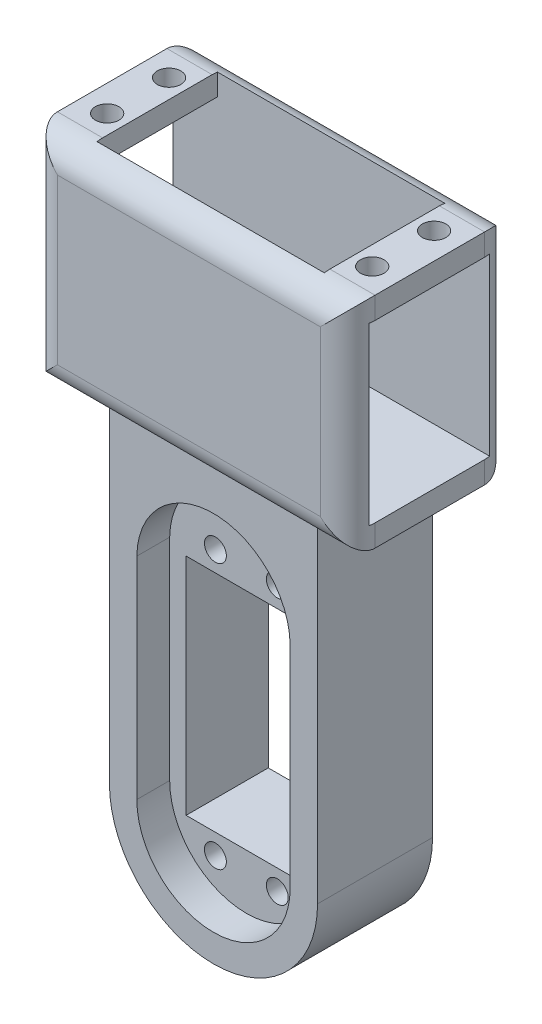
SolidWorks part; units mm, degrees
ref_plane "Front Plane" through (0, 0, 0) normal (0, 0, 1) x (1, 0, 0)
ref_plane "Top Plane" through (0, 0, 0) normal (0, 1, 0) x (1, 0, 0)
ref_plane "Right Plane" through (0, 0, 0) normal (1, 0, 0) x (0, 0, -1)
sketch "Sketch1" plane through (0, 0, 0) normal (0, 0, 1) x (1, 0, 0)
  line L1 (0, 0) -> (38, 0)
  line L2 (0, 0) -> (0, 120)
  line L3 (0, 120) -> (38, 120)
  line L4 (38, 0) -> (38, 120)
  dimension "D1" = 120
  dimension "D2" = 38
extrude "Boss-Extrude1" add sketch "Sketch1" along normal blind 13
fillet "Fillet1" radius 19 2 edges at (38, 0, 6.5) (0, 0, 6.5)
sketch "Sketch2" plane through (0, 0, 13) normal (0, 0, 1) x (1, 0, 0)
  line L0 (33, 19) -> (33, 115)
  line L1 (33, 115) -> (5, 115)
  line L2 (5, 115) -> (5, 19)
  line L3 (38, 19) -> (38, 120)
  line L4 (38, 120) -> (0, 120)
  line L5 (0, 120) -> (0, 19)
  line L6 (38, 19) -> (38, 120)
  line L7 (38, 120) -> (0, 120)
  line L8 (0, 120) -> (0, 19)
  line L9 (38, 72) -> (0, 72)
  arc A0 (5, 19) -> (19, 5) centre (19, 19) ccw
  arc A1 (19, 5) -> (33, 19) centre (19, 19) ccw
  arc A2 (0, 19) -> (19, 0) centre (19, 19) ccw
  arc A3 (19, 0) -> (38, 19) centre (19, 19) ccw
  arc A4 (0, 19) -> (19, 0) centre (19, 19) ccw
  arc A6 (19, 0) -> (38, 19) centre (19, 19) ccw construction
  arc A7 (19, 0) -> (38, 19) centre (19, 19) ccw
  arc A8 (19, 0) -> (38, 19) centre (19, 19) ccw construction
  point P15 (33, 67)
  arc M11 (0, 19) -> (19, 0) centre (19, 19) ccw
  arc M12 (19, 0) -> (38, 19) centre (19, 19) ccw
  line M13 (38, 19) -> (38, 120)
  line M14 (38, 120) -> (0, 120)
  line M15 (0, 120) -> (0, 19)
  dimension "D3" = 5
  dimension "D1" = 0
  dimension "D2" = 5
extrude "Boss-Extrude2" add sketch "Sketch2" along normal blind 8 contours A1 A0 L2 L9 L8 L0 M11 M12 M13 | L9 L6 L2 L1 L0 M14 M15 | L9 L0 L1 L2 region at (33.8141, 45.5, 13) region at (19, 93.5, 13) region at (33.6122, 93.5, 13)
sketch "Sketch3" plane through (0, 0, 13) normal (0, 0, 1) x (1, 0, 0)
  line L1 (5, 57) -> (5, 19)
  line L2 (33, 19) -> (33, 57)
  line L3 (5, 72) -> (5, 19) construction
  line L6 (33, 72) -> (5, 72)
  line L7 (5, 72) -> (5, 19)
  line L8 (33, 19) -> (33, 72)
  line L9 (33, 72) -> (5, 72)
  line L10 (5, 72) -> (5, 19)
  line L11 (33, 19) -> (33, 72)
  arc A7 (33, 57) -> (5, 57) centre (19, 57.2426) ccw
  arc A9 (5, 19) -> (33, 19) centre (19, 19) ccw
  arc A11 (5, 19) -> (33, 19) centre (19, 19) ccw
  arc A12 (5, 19) -> (33, 19) centre (19, 19) ccw
  arc A13 (5, 19) -> (33, 19) centre (19, 19) ccw construction
  arc M8 (5, 19) -> (33, 19) centre (19, 19) ccw
  line M9 (33, 19) -> (33, 72)
  line M11 (5, 72) -> (5, 19)
  line M21 (33, 72) -> (5, 72)
  dimension "D2" = 14.0021
  dimension "38" = 38
  dimension "D8" = 0
sketch "Sketch4" plane through (0, 120, 0) normal (0, 1, 0) x (1, 0, 0)
  line L0 (19, -21) -> (19, 30) construction
  line L1 (-10, 4.5) -> (48, 4.5)
  line L2 (-10, 4.5) -> (-10, -25.5)
  line L3 (-10, -25.5) -> (48, -25.5)
  line L4 (48, 4.5) -> (48, -25.5)
  line L5 (38, -21) -> (0, -21) construction
  line L6 (38, -10.5) -> (53.9489, -10.5) construction
  line L7 (38, -21) -> (38, 0) construction
  line L8 (48, -10.5) -> (49.4174, -10.5) construction
  line L15 (19, -21.5) -> (19, 0.5) construction
  line L16 (-1.75, 0.5) -> (39.75, 0.5)
  line L17 (-1.75, 0.5) -> (-1.75, -21.5)
  line L18 (-1.75, -21.5) -> (39.75, -21.5)
  line L19 (39.75, 0.5) -> (39.75, -21.5)
  line L20 (39.75, -10.5) -> (-1.75, -10.5) construction
  point P8 (19, 4.5)
  line M11 (38, 0) -> (0, 0)
  line M12 (0, 0) -> (0, -21)
  line M13 (0, -21) -> (38, -21)
  line M14 (38, -21) -> (38, 0)
  dimension "D1" = 58
  dimension "D2" = 30
  dimension "D3" = 41.5
  dimension "D4" = 22
extrude "Boss-Extrude3" add sketch "Sketch4" against normal blind 40 contours L4 L1 L2 L3 L16 L19 L18 L17 | L17 L16 L19 L18 region at (19, 120, -3.847)
extrude "Cut-Extrude2" cut sketch "Sketch4<2>" against normal blind 35 contours M14 M11 M12 M13 | L19 L16 L17 L18 M11 M14 M13 M12 region at (19, 120, -0.0303) region at (19, 120, 10.5)
sketch "Sketch4<2>" plane through (0, 120, 0) normal (0, 1, 0) x (1, 0, 0) same geometry as "Sketch4"
sketch "Sketch5" plane through (-10, 0, 0) normal (-1, 0, 0) x (0, 0, 1)
  line L0 (21.5, 116) -> (-0.5, 116)
  line L1 (-0.5, 116) -> (-0.5, 84)
  line L2 (-0.5, 84) -> (21.5, 84)
  line L3 (21.5, 84) -> (21.5, 116)
  line L4 (25.5, 120) -> (-4.5, 120)
  line L5 (-4.5, 120) -> (-4.5, 80)
  line L6 (-4.5, 80) -> (25.5, 80)
  line L7 (25.5, 80) -> (25.5, 120)
  line L8 (25.5, 120) -> (-4.5, 120)
  line L9 (-4.5, 120) -> (-4.5, 80)
  line L10 (-4.5, 80) -> (25.5, 80)
  line L11 (25.5, 80) -> (25.5, 120)
  dimension "D1" = 0
  dimension "D2" = 4
extrude "Cut-Extrude3" cut sketch "Sketch5" against normal up to next contours L0 L1 L2 L3
sketch "Sketch6" plane through (0, 120, 0) normal (0, 1, 0) x (1, 0, 0)
  line L4 (48, -25.5) -> (48, 4.5)
  line L5 (48, 4.5) -> (-10, 4.5)
  line L6 (-10, 4.5) -> (-10, -25.5)
  line L7 (-10, -25.5) -> (48, -25.5)
  line L8 (48, -25.5) -> (48, 4.5)
  line L9 (48, 4.5) -> (-10, 4.5)
  line L10 (-10, 4.5) -> (-10, -25.5)
  line L11 (-10, -25.5) -> (48, -25.5)
  dimension "D1" = 0
sketch "Sketch7" plane through (0, 120, 0) normal (0, 1, 0) x (1, 0, 0)
  line L58 (-10, -25.5) -> (48, -25.5) construction
  line L59 (19, 4.5) -> (19, -25.5) construction
  line L60 (48, 4.5) -> (-10, 4.5) construction
  circle A20 centre (-5.2, -4.92) radius 2.15
  circle A21 centre (-5.2, -16.22) radius 2.15
  circle A22 centre (43.2, -4.92) radius 2.15
  circle A23 centre (43.2, -16.22) radius 2.15
  line B0 (-8.2, -10.07) -> (-1.25, -10.07)
  line B1 (-1.25, -10.07) -> (-1.25, -1.17)
  line B2 (-1.2447, -1.0972) -> (-7.2, -1.0972)
  line B3 (-8.2, -2.0972) -> (-8.2, -3.77)
  line B4 (-8.2, -3.77) -> (-7.0166, -3.77)
  line B5 (-7.0166, -6.07) -> (-8.2, -6.07)
  line B6 (-8.2, -6.07) -> (-8.2, -10.07)
  line B7 (-1.25, -19.97) -> (-1.25, -11.07)
  line B8 (-1.25, -11.07) -> (-8.2, -11.07)
  line B9 (-8.2, -11.07) -> (-8.2, -15.07)
  line B10 (-8.2, -15.07) -> (-7.0166, -15.07)
  line B11 (-7.0166, -17.37) -> (-8.2, -17.37)
  line B12 (-8.2, -17.37) -> (-8.2, -18.97)
  line B13 (-7.2, -19.97) -> (-1.25, -19.97)
  arc B14 (-1.2447, -1.0972) -> (-1.25, -1.17) centre (-0.75, -1.17) ccw
  arc B15 (-7.2, -1.0972) -> (-8.2, -2.0972) centre (-7.2, -2.0972) ccw
  arc B16 (-7.0166, -6.07) -> (-7.0166, -3.77) centre (-5.2, -4.92) ccw
  arc B17 (-7.0166, -17.37) -> (-7.0166, -15.07) centre (-5.2, -16.22) ccw
  arc B18 (-8.2, -18.97) -> (-7.2, -19.97) centre (-7.2, -18.97) ccw
  line B19 (46.2, -10.07) -> (39.25, -10.07)
  line B20 (39.25, -10.07) -> (39.25, -1.17)
  line B21 (39.2447, -1.0972) -> (45.2, -1.0972)
  line B22 (46.2, -2.0972) -> (46.2, -3.77)
  line B23 (46.2, -3.77) -> (45.0166, -3.77)
  line B24 (45.0166, -6.07) -> (46.2, -6.07)
  line B25 (46.2, -6.07) -> (46.2, -10.07)
  line B26 (39.25, -19.97) -> (39.25, -11.07)
  line B27 (39.25, -11.07) -> (46.2, -11.07)
  line B28 (46.2, -11.07) -> (46.2, -15.07)
  line B29 (46.2, -15.07) -> (45.0166, -15.07)
  line B30 (45.0166, -17.37) -> (46.2, -17.37)
  line B31 (46.2, -17.37) -> (46.2, -18.97)
  line B32 (45.2, -19.97) -> (39.25, -19.97)
  arc B33 (39.2447, -1.0972) -> (39.25, -1.17) centre (38.75, -1.17) cw
  arc B34 (45.2, -1.0972) -> (46.2, -2.0972) centre (45.2, -2.0972) cw
  arc B35 (45.0166, -6.07) -> (45.0166, -3.77) centre (43.2, -4.92) cw
  arc B36 (45.0166, -17.37) -> (45.0166, -15.07) centre (43.2, -16.22) cw
  arc B37 (46.2, -18.97) -> (45.2, -19.97) centre (45.2, -18.97) cw
  dimension "D1" = 48.4
  dimension "D2" = 5.53
sketch_block_instance "Block3-1"
sketch_block "Block3"
sketch_block_instance "Block3-2"
extrude "Cut-Extrude4" cut sketch "Sketch7" against normal up to next contours A20 | A21 | A22 | A23 A20 region at (-5.2, 120, 4.92) region at (-5.2, 120, 16.22) region at (43.2, 120, 4.92) region at (43.2, 120, 16.22)
fillet "Fillet2" radius 5 8 edges at (-10, 100, -4.5) (19, 80, -4.5) (48, 100, -4.5) (19, 120, -4.5) (48, 100, 25.5) (19, 80, 25.5) (-10, 100, 25.5) (19, 120, 25.5)
extrude "Cut-Extrude5" cut sketch "Sketch3<3>" against normal blind 8 contours A7 L10 M9 M11 M8 region at (19, 38.1228, 13)
sketch "Sketch3<3>" plane through (0, 0, 13) normal (0, 0, 1) x (1, 0, 0) same geometry as "Sketch3"
extrude "Boss-Extrude4" add sketch "Sketch3" along normal up to surface (8 mm away) contours A7 M9 M21 M11 region at (5.3154, 64.7426, 13)
sketch "Sketch9" plane through (0, 0, 5) normal (0, 0, 1) x (1, 0, 0)
  line L1 (30, 15) -> (8, 15)
  line L2 (11.6099, 27.3489) -> (11.6099, 26.5034)
  line L3 (16.6089, 27.2486) -> (16.6089, 26.4031)
  line L4 (8, 15) -> (8, 56)
  line L5 (8, 56) -> (30, 56)
  line L6 (30, 56) -> (30, 15)
  line L7 (19, 5) -> (19, 20.515) construction
  line L8 (19, 15) -> (19, 16.6479) construction
  arc A2 (5, 19) -> (33, 19) centre (19, 19) ccw construction
  arc A6 (11.6099, 27.3489) -> (16.6089, 27.2486) centre (14.1094, 27.2998) cw
  arc A7 (16.6089, 26.4031) -> (11.6099, 26.5034) centre (14, 21) cw
  dimension "D3" = 41
  dimension "D5" = 6
  dimension "D6" = 2.5
  dimension "D2" = 10
  dimension "D4" = 22
  dimension "D7" = 0.8455
  dimension "D8" = 0.8455
  dimension "D9" = 6.2998
  dimension "D10" = 6.3008
extrude "Cut-Extrude20" cut sketch "Sketch9" against normal through all contours L4 A7 L2 A6 L3 L6 L5 | L6 A7 L1 | L1 A7 L4 | A7 L2 A6 L3 region at (19.9099, 37.9427, 5) region at (9.3402, 16.3402, 5)
sketch "Sketch11" plane through (0, 0, 5) normal (0, 0, 1) x (1, 0, 0)
  line L1 (19, 56) -> (19, 15) construction
  line L2 (8, 35.5) -> (30, 35.5) construction
  line L3 (8, 56) -> (30, 56) construction
  line L4 (8, 15) -> (8, 56) construction
  line L7 (30, 56) -> (30, 15) construction
  line L8 (30, 15) -> (8, 15) construction
  line L9 (30, 56) -> (30, 15)
  line L10 (30, 15) -> (8, 15)
  line L11 (8, 15) -> (8, 56)
  line L12 (8, 56) -> (30, 56)
  circle A0 centre (13.35, 59.7) radius 2
  circle A6 centre (24.65, 59.7) radius 2
  circle A7 centre (24.65, 11.3) radius 2
  circle A8 centre (13.35, 11.3) radius 2
  dimension "D1" = 4
  dimension "D2" = 11.3
  dimension "D3" = 48.4
extrude "Cut-Extrude22" cut sketch "Sketch11" against normal through all both and the other way through all
sketch "Sketch12" plane through (0, 0, 5) normal (0, 0, 1) x (1, 0, 0)
  line L0 (30, 15) -> (8, 15) construction
  line L1 (30, 15) -> (8, 15)
  line L2 (33, 19) -> (33, 57.4851)
  line L3 (5, 57.4851) -> (5, 19)
  line L4 (33, 19) -> (33, 57.4851)
  line L5 (5, 57.4851) -> (5, 19)
  line L6 (8, 56) -> (30, 56) construction
  line L7 (8, 15) -> (8, 56) construction
  line L8 (30, 56) -> (30, 15) construction
  line L9 (30, 56) -> (30, 15)
  line L10 (8, 15) -> (8, 56)
  line L11 (8, 56) -> (30, 56)
  circle A0 centre (13.35, 11.3) radius 2 construction
  circle A1 centre (24.65, 11.3) radius 2 construction
  arc A2 (33, 57.4851) -> (5, 57.4851) centre (19, 57.2426) ccw
  arc A3 (5, 19) -> (33, 19) centre (19, 19) ccw
  arc A4 (33, 57.4851) -> (5, 57.4851) centre (19, 57.2426) ccw
  arc A5 (5, 19) -> (33, 19) centre (19, 19) ccw
  circle A6 centre (24.65, 11.3) radius 2
  circle A7 centre (13.35, 11.3) radius 2
  circle A8 centre (13.35, 59.7) radius 2 construction
  circle A9 centre (13.35, 59.7) radius 2
  circle A10 centre (24.65, 59.7) radius 2 construction
  circle A11 centre (24.65, 59.7) radius 2
  dimension "D1" = 0
extrude "Boss-Extrude6" add sketch "Sketch12" along normal blind 10
